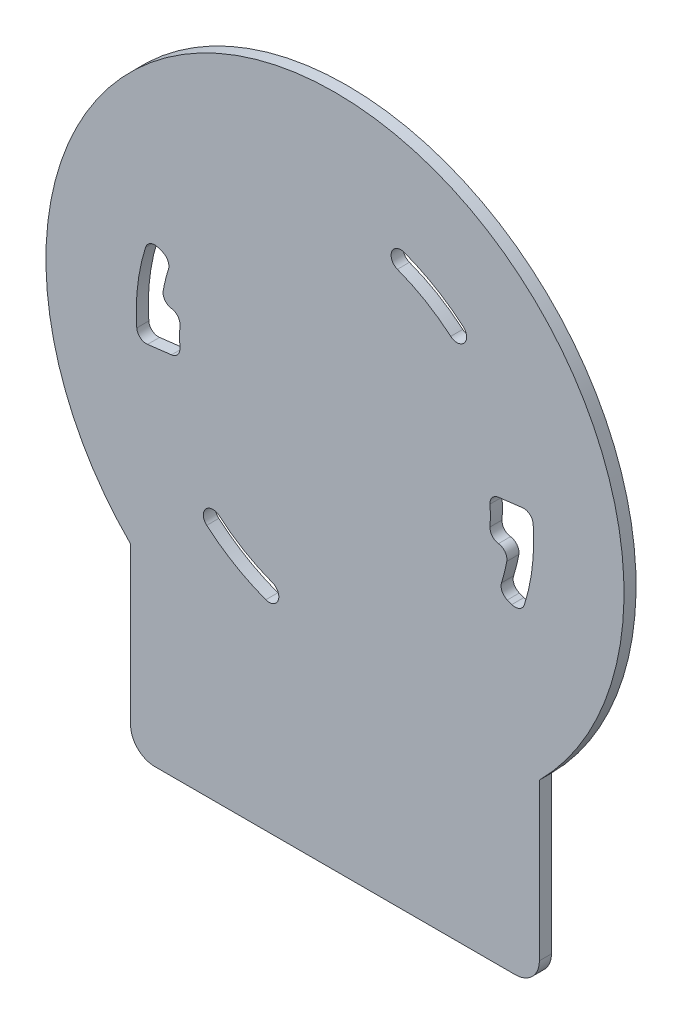
SolidWorks part; units mm, degrees
ref_plane "Front Plane" through (0, 0, 0) normal (0, 0, 1) x (1, 0, 0)
ref_plane "Top Plane" through (0, 0, 0) normal (0, 1, 0) x (1, 0, 0)
ref_plane "Right Plane" through (0, 0, 0) normal (1, 0, 0) x (0, 0, -1)
sketch "Sketch1" plane through (0, 0, 0) normal (0, 0, 1) x (1, 0, 0)
  line L0 (0, -38.4823) -> (0, 38.4823) construction
  line L1 (-18.1008, 0) -> (18.1008, 0) construction
  line L2 (15.4551, -5.7784) -> (0, 0) construction
  line L3 (16.377, 2.0108) -> (0, 0) construction
  line L4 (16.377, 2.0108) -> (12.8038, 1.5721)
  line L5 (12.8038, -1.5721) -> (0, 0) construction
  line L6 (12.8038, -1.5721) -> (14.3919, -1.7671)
  line L7 (15.4551, -5.7784) -> (13.5817, -5.078)
  line L8 (-16.9706, -16.9706) -> (0, 0) construction
  line L9 (16.9706, -16.9706) -> (0, 0) construction
  line L10 (-16.9706, -16.9706) -> (-16.9706, -29.9706)
  line L11 (16.9706, -16.9706) -> (16.9706, -29.9706)
  line L12 (-14.9706, -31.9706) -> (14.9706, -31.9706)
  line L16 (-16.377, -2.0108) -> (-12.8038, -1.5721)
  line L17 (-15.4551, 5.7784) -> (-13.5817, 5.078)
  line L18 (-12.8038, 1.5721) -> (-14.3919, 1.7671)
  line L19 (-9.6118, -11.254) -> (0, 0) construction
  line L20 (-5.1831, -13.8627) -> (0, 0) construction
  line L21 (5.4632, 14.6121) -> (0, 0) construction
  line L22 (10.1314, 11.8623) -> (0, 0) construction
  arc A0 (15.4551, -5.7784) -> (16.377, 2.0108) centre (0, 0) ccw
  arc A1 (12.8038, 1.5721) -> (12.8038, -1.5721) centre (0, 0) cw
  arc A2 (13.5817, -5.078) -> (14.3919, -1.7671) centre (0, 0) ccw
  arc A4 (16.9706, -16.9706) -> (-16.9706, -16.9706) centre (0, 0) ccw
  arc A5 (-16.9706, -29.9706) -> (-14.9706, -31.9706) centre (-14.9706, -29.9706) ccw
  arc A6 (14.9706, -31.9706) -> (16.9706, -29.9706) centre (14.9706, -29.9706) ccw
  arc A7 (-12.8038, 1.5721) -> (-12.8038, -1.5721) centre (0, 0) ccw
  arc A10 (-15.4551, 5.7784) -> (-16.377, -2.0108) centre (0, 0) ccw
  arc A11 (-13.5817, 5.078) -> (-14.3919, 1.7671) centre (0, 0) ccw
  arc A12 (-9.6118, -11.254) -> (-5.1831, -13.8627) centre (0, 0) ccw
  arc A13 (-10.6509, -12.4707) -> (-5.7434, -15.3614) centre (0, 0) ccw
  arc A14 (-9.6118, -11.254) -> (-10.6509, -12.4707) centre (-10.1314, -11.8623) ccw
  arc A15 (-5.7434, -15.3614) -> (-5.1831, -13.8627) centre (-5.4632, -14.6121) ccw
  arc A16 (5.7434, 15.3614) -> (5.1831, 13.8627) centre (5.4632, 14.6121) ccw
  arc A17 (9.6118, 11.254) -> (5.1831, 13.8627) centre (0, 0) ccw
  arc A18 (9.6118, 11.254) -> (10.6509, 12.4707) centre (10.1314, 11.8623) ccw
  arc A19 (10.6509, 12.4707) -> (5.7434, 15.3614) centre (0, 0) ccw
  point P7 (0, 0)
  point P10 (0, 0)
  point P43 (0, 0)
  dimension "D1" = 16.5
  dimension "D6" = 24
  dimension "D12" = 2
  dimension "D13" = 16.5
  dimension "D14" = 14.5
  dimension "D15" = 14.8
  dimension "D18" = 16.4
  dimension "D2" = 20.5
  dimension "D3" = 7
  dimension "D4" = 3.6
  dimension "D5" = 7
  dimension "D7" = 2
  dimension "D8" = 45
  dimension "D9" = 45
  dimension "D10" = 13
  dimension "D11" = 13
  dimension "D16" = 42.5
  dimension "D17" = 20
  dimension "D20" = 42.5
  dimension "D19" = 2
extrude "Outline" add sketch "Sketch1" along normal blind 1
fillet "Fillets" radius 0.8 12 edges at (16.377, 2.0108, 0.5) (12.8038, 1.5721, 0.5) (13.5817, -5.078, 0.5) (15.4551, -5.7784, 0.5) (14.3919, -1.7671, 0.5) (12.8038, -1.5721, 0.5) (-12.8038, -1.5721, 0.5) (-16.377, -2.0108, 0.5) (-15.4551, 5.7784, 0.5) (-13.5817, 5.078, 0.5) (-12.8038, 1.5721, 0.5) (-14.3919, 1.7671, 0.5)
